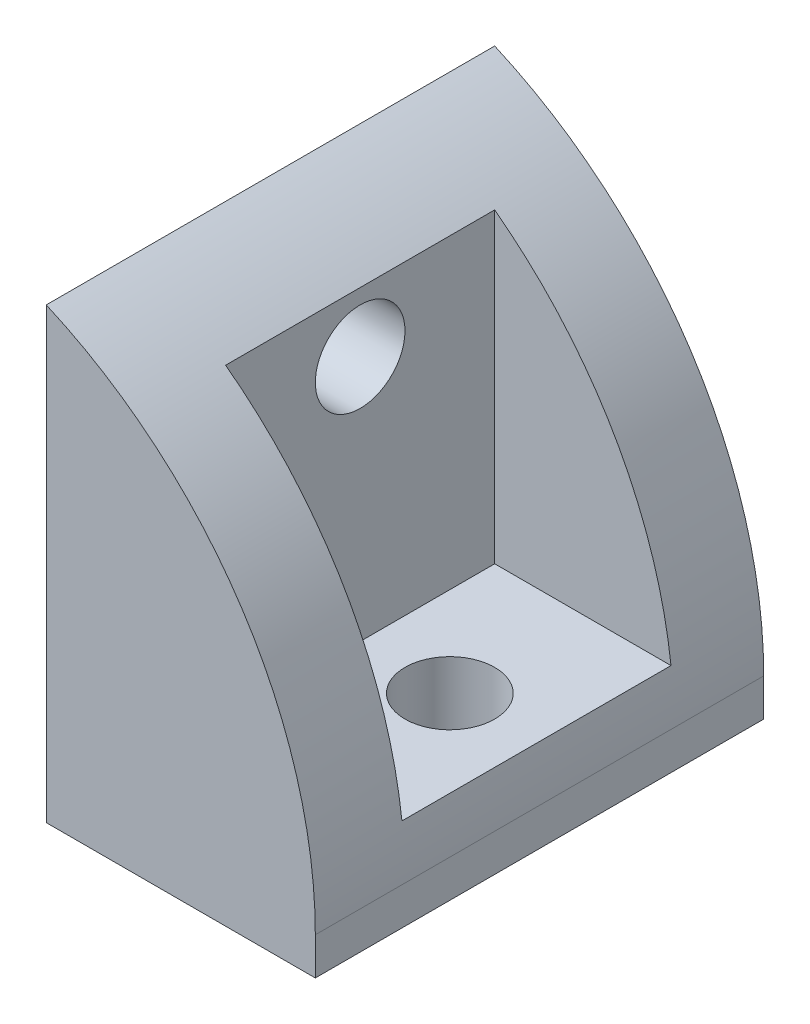
SolidWorks part; units mm, degrees
ref_plane "Alzado" through (0, 0, 0) normal (0, 0, 1) x (1, 0, 0)
ref_plane "Planta" through (0, 0, 0) normal (0, 1, 0) x (1, 0, 0)
ref_plane "Vista lateral" through (0, 0, 0) normal (1, 0, 0) x (0, 0, -1)
sketch "Croquis1" plane through (0, 0, 0) normal (0, 1, 0) x (1, 0, 0)
  line L0 (6, 2) -> (2, 2)
  line L1 (0, 0) -> (6, 0)
  line L2 (0, 0) -> (0, 10)
  line L3 (0, 10) -> (6, 10)
  line L4 (6, 0) -> (6, 10)
  line L5 (2, 2) -> (2, 8)
  line L6 (2, 8) -> (6, 8)
  circle A0 centre (4, 5) radius 1
  point P8 (6, 5)
  point P15 (4, 8)
  point P16 (2, 5)
  point P17 (0, 5)
  dimension "D3" = 2
  dimension "D1" = 6
  dimension "D2" = 10
  dimension "D6" = 4
  dimension "D7" = 2
extrude "Saliente-Extruir1" add sketch "Croquis1" against normal blind 2 contours L6 L5 L0 L4 A0 | L5 L6 L4 L3 L2 L1 L0 region at (5.8834, 0, -1) region at (4, 0, -2.0721)
extrude "Saliente-Extruir2" add sketch "Croquis1<3>" along normal blind 8 contours L5 L6 L4 L3 L2 L1 L0 region at (5.8834, 0, -1)
sketch "Croquis1<3>" plane through (0, 0, 0) normal (0, 1, 0) x (1, 0, 0) same geometry as "Croquis1"
sketch "Croquis2" plane through (2, 0, 0) normal (1, 0, 0) x (0, 0, -1)
  line L0 (2, 8) -> (8, 8) construction
  circle A0 centre (5, 5.5) radius 1
  point P5 (5, 8)
  dimension "D1" = 2
  dimension "D2" = 2.5
extrude "Cortar-Extruir1" cut sketch "Croquis2" against normal through all
fillet "Redondeo1" radius 10 1 edges at (6, 8, -1)
